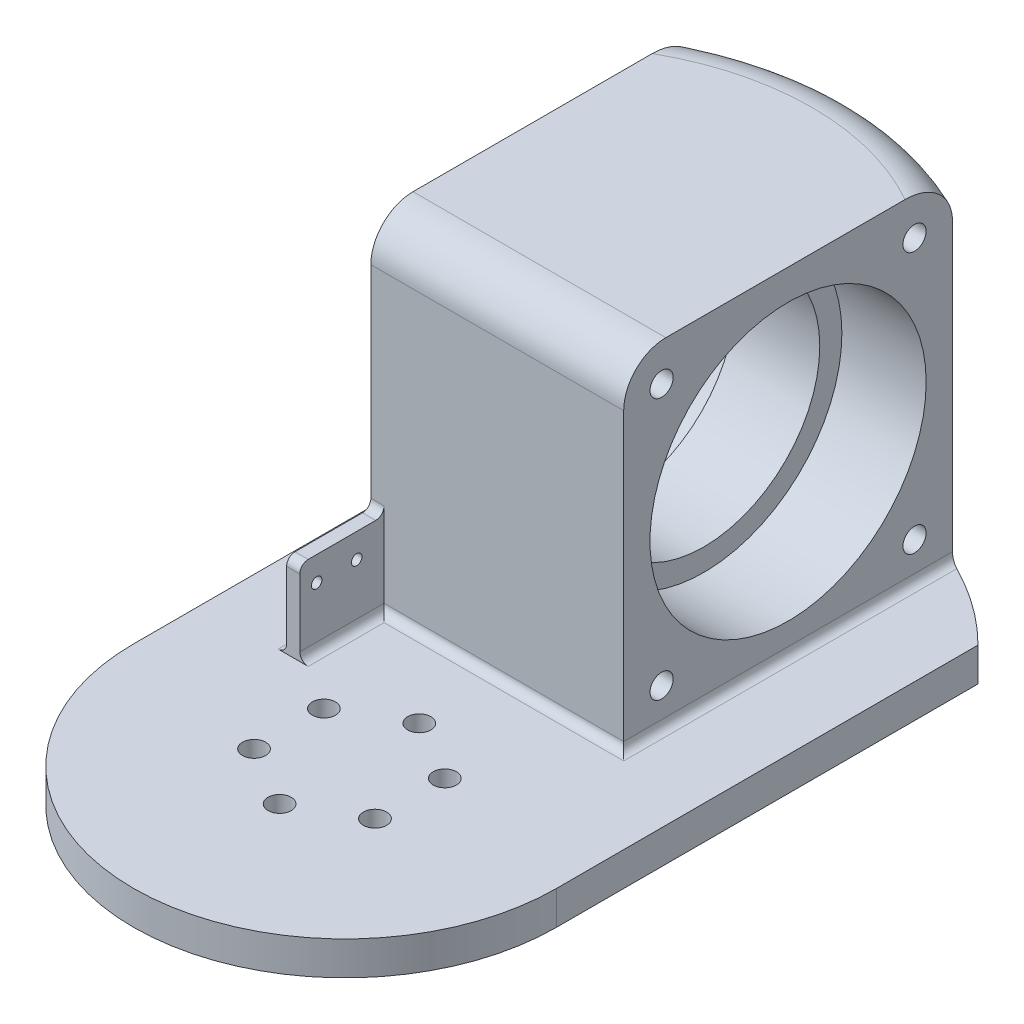
SolidWorks part; units mm, degrees
ref_plane "Front Plane" through (0, 0, 0) normal (0, 0, 1) x (1, 0, 0)
ref_plane "Top Plane" through (0, 0, 0) normal (0, 1, 0) x (1, 0, 0)
ref_plane "Right Plane" through (0, 0, 0) normal (1, 0, 0) x (0, 0, -1)
sketch "Sketch3" plane through (0, 0, 0) normal (0, 1, 0) x (1, 0, 0)
  circle A1 centre (0, 1.0493) radius 44.22
  circle A3 centre (0, 17.6193) radius 2.75
  circle A4 centre (14.35, 9.3343) radius 2.75
  circle A5 centre (14.35, -7.2357) radius 2.75
  circle A6 centre (0, -15.5207) radius 2.75
  circle A7 centre (-14.35, -7.2357) radius 2.75
  circle A8 centre (-14.35, 9.3343) radius 2.75
  dimension "D2" = 88.44
extrude "Boss-Extrude1" add sketch "Sketch3" along normal blind 1
sketch "Sketch4" plane through (0, 1, 0) normal (0, 1, 0) x (1, 0, 0)
  line L0 (-50.22, 0) -> (-50.22, 100)
  line L2 (50.22, 100) -> (50.22, 0)
  arc A1 (50.22, 0) -> (-50.22, 0) centre (0, 0) cw
  arc A2 (-50.22, 100) -> (50.22, 100) centre (0, 49.78) cw
extrude "Boss-Extrude2" add sketch "Sketch4" along normal blind 8
sketch "Sketch9" plane through (0, 0, 0) normal (0, -1, 0) x (1, 0, 0)
  circle A0 centre (0, 15.5207) radius 2.75
  circle A1 centre (14.35, 7.2357) radius 2.75
  circle A2 centre (14.35, -9.3343) radius 2.75
  circle A3 centre (0, -17.6193) radius 2.75
  circle A4 centre (-14.35, -9.3343) radius 2.75
  circle A5 centre (-14.35, 7.2357) radius 2.75
extrude "Cut-Extrude2" cut sketch "Sketch9" against normal blind 20
sketch "Sketch11" plane through (0, 9, 0) normal (0, 1, 0) x (1, 0, 0)
  line L4 (0, 36.1354) -> (-30, 36.1354)
  line L9 (-30, 36.1354) -> (-30, 114.1547)
  line L10 (0, 36.1354) -> (30, 36.1354)
  line L11 (30, 36.1354) -> (30, 114.1547)
  arc A0 (50.22, 100) -> (-50.22, 100) centre (0, 49.78) ccw construction
  arc A2 (-30, 114.1547) -> (30, 114.1547) centre (0, 49.78) cw
extrude "Boss-Extrude3" add sketch "Sketch11" along normal blind 80
sketch "Sketch12" plane through (-20, 0, 0) normal (-1, 0, 0) x (0, 0, 1)
  line L8 (-39.9083, 89) -> (-39.9083, 9)
  line L9 (-36.1354, 89) -> (-114.1547, 89)
  line L10 (-36.1354, 89) -> (-36.1354, 9)
  line L11 (-36.1354, 9) -> (-114.1547, 9)
  line L12 (-114.1547, 89) -> (-114.1547, 9)
  circle A0 centre (-75.1444, 49) radius 32.774
  dimension "D1" = 39.009
extrude "Cut-Extrude3" cut sketch "Sketch12" against normal blind 10 and the other way blind 10 contours A0
sketch "Sketch13" plane through (30, 0, 0) normal (1, 0, 0) x (0, 0, -1)
  line L1 (36.1354, 89) -> (114.1547, 89)
  line L2 (36.1354, 89) -> (36.1354, 9)
  line L3 (36.1354, 9) -> (114.1547, 9)
  line L4 (114.1547, 89) -> (114.1547, 9)
  circle A0 centre (75.145, 49) radius 32.774
  circle A1 centre (75.145, 49) radius 27.524
  dimension "D1" = 5.25
  dimension "D2" = 65.548
  dimension "D3" = 39.0096
extrude "Cut-Extrude4" cut sketch "Sketch13" against normal blind 20 contours A0
extrude "Cut-Extrude5" cut sketch "Sketch13<3>" against normal blind 66 contours A1 region at (30, 49, -75.145)
sketch "Sketch13<3>" plane through (30, 0, 0) normal (1, 0, 0) x (0, 0, -1) same geometry as "Sketch13"
sketch "Sketch14" plane through (0, 9, 0) normal (0, 1, 0) x (1, 0, 0)
  line L1 (-30, 36.1354) -> (-26.865, 36.1354)
  line L2 (-30, 36.1354) -> (-30, 16.1354)
  line L3 (-30, 16.1354) -> (-26.865, 16.1354)
  line L4 (-26.865, 36.1354) -> (-26.865, 16.1354)
extrude "Boss-Extrude4" add sketch "Sketch14" along normal blind 20
extrude "Cut-Extrude6" cut sketch "Sketch3<4>" along normal blind 1
sketch "Sketch3<4>" plane through (0, 0, 0) normal (0, 1, 0) x (1, 0, 0) same geometry as "Sketch3"
sketch "Sketch15" plane through (-30, 0, 0) normal (-1, 0, 0) x (0, 0, 1)
  line L1 (-16.1354, 29) -> (-16.1354, 9) construction
  line L2 (-33.6354, 29) -> (-33.6354, 14)
  line L3 (-114.1547, 14) -> (-16.1354, 14) construction
  circle A0 centre (-20.1354, 23.2015) radius 1.25
  circle A1 centre (-29.6354, 23.2015) radius 1.25
  dimension "D1" = 4
  dimension "D2" = 9.5
extrude "Cut-Extrude7" cut sketch "Sketch15" against normal blind 10 contours A1 | A0 region at (-30, 23.2015, -20.1354) region at (-30, 23.2015, -29.6354)
sketch "Sketch17" plane through (30, 0, 0) normal (1, 0, 0) x (0, 0, -1)
  line L0 (36.1354, 89) -> (36.1354, 9) construction
  line L1 (45.1354, 80) -> (105.1547, 80)
  line L2 (45.1354, 80) -> (45.1354, 18)
  line L3 (45.1354, 18) -> (105.1547, 18)
  line L4 (105.1547, 80) -> (105.1547, 18)
  line L5 (114.1547, 89) -> (114.1547, 9) construction
  line L6 (36.1354, 89) -> (114.1547, 89) construction
  line L8 (36.1354, 9) -> (114.1547, 9) construction
  circle A0 centre (45.1354, 80) radius 2.75
  circle A1 centre (105.1547, 80) radius 2.75
  circle A2 centre (105.1547, 18) radius 2.75
  circle A3 centre (45.1354, 18) radius 2.75
  dimension "D1" = 9
  dimension "D2" = 9
  dimension "D3" = 9
  dimension "D4" = 9
extrude "Cut-Extrude8" cut sketch "Sketch17" against normal blind 83 contours L2 A0 L1 | L1 A1 L4 | L4 A2 L3 | L3 A3 L2 | L2 A3 L3 | L3 A2 L4 | L4 A1 L1 | L1 A0 L2 region at (30, 80.389, -44.7463) region at (30, 78.8329, -46.3025) region at (30, 80.389, -105.5437) region at (30, 78.8329, -103.9875) region at (30, 19.1671, -46.3025) region at (30, 17.611, -44.7463) region at (30, 17.611, -105.5437) region at (30, 19.1671, -103.9875)
sketch "Sketch18" plane through (-30, 0, 0) normal (-1, 0, 0) x (0, 0, 1)
  circle A0 centre (-105.1547, 80) radius 6.25
  circle A1 centre (-45.1354, 80) radius 6.25
  circle A2 centre (-45.1354, 18) radius 6.25
  circle A3 centre (-105.1547, 18) radius 6.25
extrude "Cut-Extrude9" cut sketch "Sketch18" against normal blind 5.5
fillet "Fillet1" radius 10 2 edges at (0, 89, -120.8018) (0, 89, -36.1354)
fillet "Fillet2" radius 2 4 edges at (-26.865, 9, -26.1354) (1.5675, 9, -36.1354) (30, 9, -75.145) (-30, 9, -65.145)
fillet "Fillet3" radius 2 2 edges at (-28.4325, 29, -36.1354) (-28.4325, 29, -16.1354)
sketch "Sketch19" plane through (0, 9, 0) normal (0, 1, 0) x (1, 0, 0)
  arc A0 (50.22, 0) -> (-50.22, 0) centre (0, 0) cw
sketch "Sketch20" plane through (30, 0, 0) normal (1, 0, 0) x (0, 0, -1)
  arc A0 (42.371, 49) -> (107.919, 49) centre (75.145, 49) ccw
  circle A1 centre (75.145, 49) radius 32.774 construction
